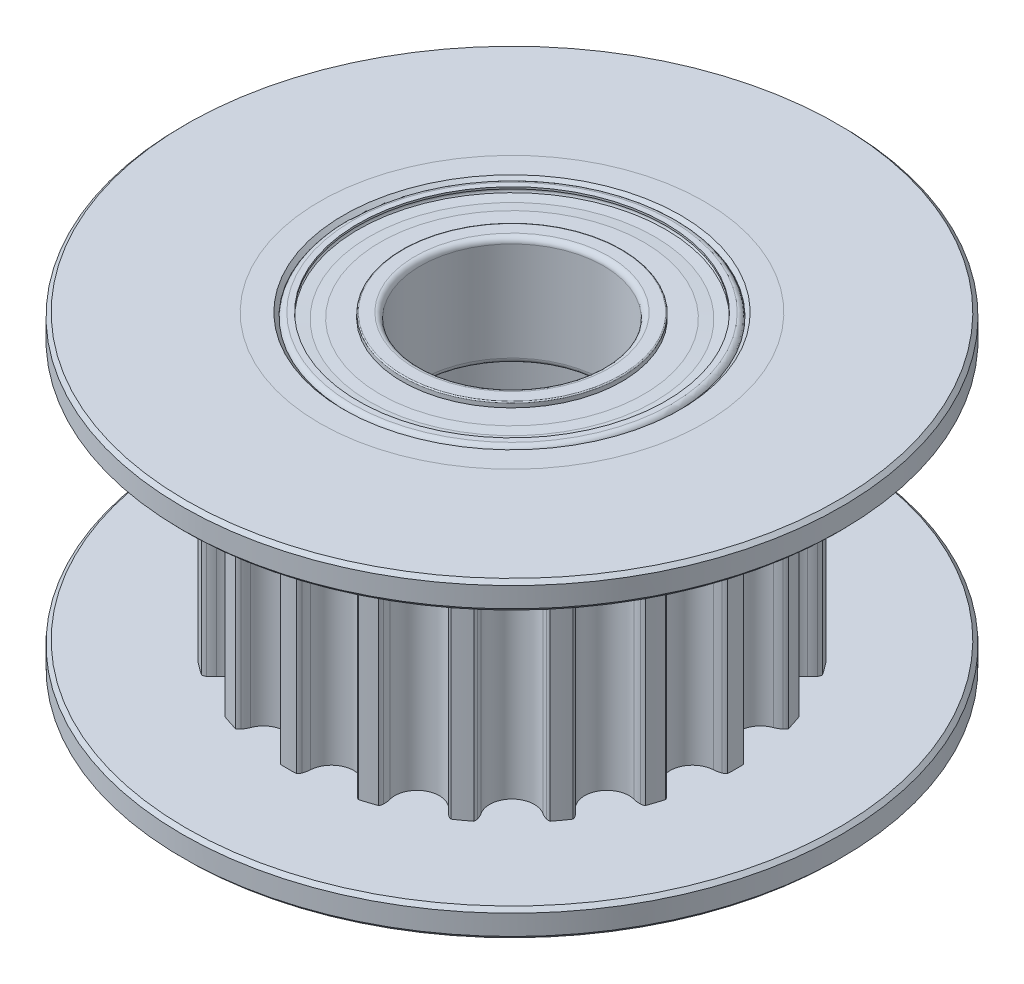
SolidWorks part; units mm, degrees
material "6061-T6 (SS)"
ref_plane "Přední rovina" through (0, 0, 0) normal (0, 0, 1) x (1, 0, 0)
ref_plane "Horní rovina" through (0, 0, 0) normal (0, 1, 0) x (1, 0, 0)
ref_plane "Pravá rovina" through (0, 0, 0) normal (1, 0, 0) x (0, 0, -1)
sketch "Skica1" plane through (0, 0, 0) normal (0, 0, 1) x (1, 0, 0)
  line L0 (4.5, 8.5) -> (5.25, 8.5)
  line L1 (5.25, 8.5) -> (5.25, 7.75)
  line L2 (5.25, 7.75) -> (6.11, 7.75)
  line L3 (6.11, 7.75) -> (6.11, 0.75)
  line L4 (6.11, 0.75) -> (5.25, 0.75)
  line L5 (5.25, 0.75) -> (5.25, 0)
  line L6 (5.25, 0) -> (4.5, 0)
  line L8 (4.5, 8.5) -> (4.5, 5.5)
  line L9 (4.5, 5.5) -> (3.5, 5.5)
  line L10 (3.5, 5.5) -> (3.5, 3)
  line L11 (3.5, 3) -> (4.5, 3)
  line L12 (4.5, 3) -> (4.5, 0)
  line L13 (0, 0) -> (0, -4.1646) construction
  dimension "D1" = 8.5
  dimension "D2" = 7
  dimension "D3" = 4.5
  dimension "D4" = 3.5
  dimension "D5" = 6.11
  dimension "D6" = 3
  dimension "D7" = 5.25
revolve "Rotovat1" add sketch "Skica1" angle 360 about L13
chamfer "Zkosení1" distance 0.1 angle 45 4 edges at (0, 3, 3.5) (0, 0, 4.5) (0, 5.5, 3.5) (0, 8.5, 4.5)
fillet "Zaoblit1" radius 0.1 2 edges at (0, 3, 4.5) (0, 5.5, 4.5)
sketch "Skica11" plane through (0, 7.75, 0) normal (0, 1, 0) x (1, 0, 0)
  line L0 (0, -55) -> (0, 55) construction
  line L1 (-55, 0) -> (55, 0) construction
  point P5 (0, 6.1087)
  arc B0 (-3.6824, -4.5256) -> (-4.5256, -3.6824) centre (-4.1938, -4.1938) ccw
  arc B1 (-3.6824, -4.5256) -> (-3.7624, -4.7003) centre (-3.1284, -4.885) ccw
  arc B2 (-3.7624, -4.7003) -> (-3.7672, -4.8088) centre (-3.5429, -4.7643) ccw
  arc B3 (-3.7672, -4.8088) -> (-3.4093, -5.0688) centre (0, 0) ccw
  arc B4 (-3.4093, -5.0688) -> (-3.3076, -5.0308) centre (-3.4362, -4.8418) ccw
  arc B5 (-3.3076, -5.0308) -> (-3.1662, -4.9006) centre (-3.6792, -4.4848) ccw
  arc B6 (-2.1037, -5.442) -> (-3.1662, -4.9006) centre (-2.6926, -5.2845) ccw
  arc B7 (-2.1037, -5.442) -> (-2.1258, -5.6329) centre (-1.4657, -5.6126) ccw
  arc B8 (-2.1258, -5.6329) -> (-2.0968, -5.7376) centre (-1.8973, -5.6259) ccw
  arc B9 (-2.0968, -5.7376) -> (-1.6761, -5.8742) centre (0, 0) ccw
  arc B10 (-1.6761, -5.8742) -> (-1.5911, -5.8066) centre (-1.7719, -5.6667) ccw
  arc B11 (-1.5911, -5.8066) -> (-1.4968, -5.6392) centre (-2.1132, -5.4022) ccw
  arc B12 (-0.319, -5.8257) -> (-1.4968, -5.6392) centre (-0.9278, -5.8579) ccw
  arc B13 (-0.319, -5.8257) -> (-0.2811, -6.0141) centre (0.3404, -5.7909) ccw
  arc B14 (-0.2811, -6.0141) -> (-0.2211, -6.1047) centre (-0.0659, -5.9369) ccw
  arc B15 (-0.2211, -6.1047) -> (0.2211, -6.1047) centre (0, 0) ccw
  arc B16 (0.2211, -6.1047) -> (0.2811, -6.0141) centre (0.0659, -5.9369) ccw
  arc B17 (0.2811, -6.0141) -> (0.319, -5.8257) centre (-0.3404, -5.7909) ccw
  arc B18 (1.4968, -5.6392) -> (0.319, -5.8257) centre (0.9278, -5.8579) ccw
  arc B19 (1.4968, -5.6392) -> (1.5911, -5.8066) centre (2.1132, -5.4022) ccw
  arc B20 (1.5911, -5.8066) -> (1.6761, -5.8742) centre (1.7719, -5.6667) ccw
  arc B21 (1.6761, -5.8742) -> (2.0968, -5.7376) centre (0, 0) ccw
  arc B22 (2.0968, -5.7376) -> (2.1258, -5.6329) centre (1.8973, -5.6259) ccw
  arc B23 (2.1258, -5.6329) -> (2.1037, -5.442) centre (1.4657, -5.6126) ccw
  arc B24 (3.1662, -4.9006) -> (2.1037, -5.442) centre (2.6926, -5.2845) ccw
  arc B25 (3.1662, -4.9006) -> (3.3076, -5.0308) centre (3.6792, -4.4848) ccw
  arc B26 (3.3076, -5.0308) -> (3.4093, -5.0688) centre (3.4362, -4.8418) ccw
  arc B27 (3.4093, -5.0688) -> (3.7672, -4.8088) centre (0, 0) ccw
  arc B28 (3.7672, -4.8088) -> (3.7624, -4.7003) centre (3.5429, -4.7643) ccw
  arc B29 (3.7624, -4.7003) -> (3.6824, -4.5256) centre (3.1284, -4.885) ccw
  arc B30 (4.5256, -3.6824) -> (3.6824, -4.5256) centre (4.1938, -4.1938) ccw
  arc B31 (4.5256, -3.6824) -> (4.7003, -3.7624) centre (4.885, -3.1284) ccw
  arc B32 (4.7003, -3.7624) -> (4.8088, -3.7672) centre (4.7643, -3.5429) ccw
  arc B33 (4.8088, -3.7672) -> (5.0688, -3.4093) centre (0, 0) ccw
  arc B34 (5.0688, -3.4093) -> (5.0308, -3.3076) centre (4.8418, -3.4362) ccw
  arc B35 (5.0308, -3.3076) -> (4.9006, -3.1662) centre (4.4848, -3.6792) ccw
  arc B36 (5.442, -2.1037) -> (4.9006, -3.1662) centre (5.2845, -2.6926) ccw
  arc B37 (5.442, -2.1037) -> (5.6329, -2.1258) centre (5.6126, -1.4657) ccw
  arc B38 (5.6329, -2.1258) -> (5.7376, -2.0968) centre (5.6259, -1.8973) ccw
  arc B39 (5.7376, -2.0968) -> (5.8742, -1.6761) centre (0, 0) ccw
  arc B40 (5.8742, -1.6761) -> (5.8066, -1.5911) centre (5.6667, -1.7719) ccw
  arc B41 (5.8066, -1.5911) -> (5.6392, -1.4968) centre (5.4022, -2.1132) ccw
  arc B42 (5.8257, -0.319) -> (5.6392, -1.4968) centre (5.8579, -0.9278) ccw
  arc B43 (5.8257, -0.319) -> (6.0141, -0.2811) centre (5.7909, 0.3404) ccw
  arc B44 (6.0141, -0.2811) -> (6.1047, -0.2211) centre (5.9369, -0.0659) ccw
  arc B45 (6.1047, -0.2211) -> (6.1047, 0.2211) centre (0, 0) ccw
  arc B46 (6.1047, 0.2211) -> (6.0141, 0.2811) centre (5.9369, 0.0659) ccw
  arc B47 (6.0141, 0.2811) -> (5.8257, 0.319) centre (5.7909, -0.3404) ccw
  arc B48 (5.6392, 1.4968) -> (5.8257, 0.319) centre (5.8579, 0.9278) ccw
  arc B49 (5.6392, 1.4968) -> (5.8066, 1.5911) centre (5.4022, 2.1132) ccw
  arc B50 (5.8066, 1.5911) -> (5.8742, 1.6761) centre (5.6667, 1.7719) ccw
  arc B51 (5.8742, 1.6761) -> (5.7376, 2.0968) centre (0, 0) ccw
  arc B52 (5.7376, 2.0968) -> (5.6329, 2.1258) centre (5.6259, 1.8973) ccw
  arc B53 (5.6329, 2.1258) -> (5.442, 2.1037) centre (5.6126, 1.4657) ccw
  arc B54 (4.9006, 3.1662) -> (5.442, 2.1037) centre (5.2845, 2.6926) ccw
  arc B55 (4.9006, 3.1662) -> (5.0308, 3.3076) centre (4.4848, 3.6792) ccw
  arc B56 (5.0308, 3.3076) -> (5.0688, 3.4093) centre (4.8418, 3.4362) ccw
  arc B57 (5.0688, 3.4093) -> (4.8088, 3.7672) centre (0, 0) ccw
  arc B58 (4.8088, 3.7672) -> (4.7003, 3.7624) centre (4.7643, 3.5429) ccw
  arc B59 (4.7003, 3.7624) -> (4.5256, 3.6824) centre (4.885, 3.1284) ccw
  arc B60 (3.6824, 4.5256) -> (4.5256, 3.6824) centre (4.1938, 4.1938) ccw
  arc B61 (3.6824, 4.5256) -> (3.7624, 4.7003) centre (3.1284, 4.885) ccw
  arc B62 (3.7624, 4.7003) -> (3.7672, 4.8088) centre (3.5429, 4.7643) ccw
  arc B63 (3.7672, 4.8088) -> (3.4093, 5.0688) centre (0, 0) ccw
  arc B64 (3.4093, 5.0688) -> (3.3076, 5.0308) centre (3.4362, 4.8418) ccw
  arc B65 (3.3076, 5.0308) -> (3.1662, 4.9006) centre (3.6792, 4.4848) ccw
  arc B66 (2.1037, 5.442) -> (3.1662, 4.9006) centre (2.6926, 5.2845) ccw
  arc B67 (2.1037, 5.442) -> (2.1258, 5.6329) centre (1.4657, 5.6126) ccw
  arc B68 (2.1258, 5.6329) -> (2.0968, 5.7376) centre (1.8973, 5.6259) ccw
  arc B69 (2.0968, 5.7376) -> (1.6761, 5.8742) centre (0, 0) ccw
  arc B70 (1.6761, 5.8742) -> (1.5911, 5.8066) centre (1.7719, 5.6667) ccw
  arc B71 (1.5911, 5.8066) -> (1.4968, 5.6392) centre (2.1132, 5.4022) ccw
  arc B72 (0.319, 5.8257) -> (1.4968, 5.6392) centre (0.9278, 5.8579) ccw
  arc B73 (0.319, 5.8257) -> (0.2811, 6.0141) centre (-0.3404, 5.7909) ccw
  arc B74 (0.2811, 6.0141) -> (0.2211, 6.1047) centre (0.0659, 5.9369) ccw
  arc B75 (0.2211, 6.1047) -> (-0.2211, 6.1047) centre (0, 0) ccw
  arc B76 (-0.2211, 6.1047) -> (-0.2811, 6.0141) centre (-0.0659, 5.9369) ccw
  arc B77 (-0.2811, 6.0141) -> (-0.319, 5.8257) centre (0.3404, 5.7909) ccw
  arc B78 (-1.4968, 5.6392) -> (-0.319, 5.8257) centre (-0.9278, 5.8579) ccw
  arc B79 (-1.4968, 5.6392) -> (-1.5911, 5.8066) centre (-2.1132, 5.4022) ccw
  arc B80 (-1.5911, 5.8066) -> (-1.6761, 5.8742) centre (-1.7719, 5.6667) ccw
  arc B81 (-1.6761, 5.8742) -> (-2.0968, 5.7376) centre (0, 0) ccw
  arc B82 (-2.0968, 5.7376) -> (-2.1258, 5.6329) centre (-1.8973, 5.6259) ccw
  arc B83 (-2.1258, 5.6329) -> (-2.1037, 5.442) centre (-1.4657, 5.6126) ccw
  arc B84 (-3.1662, 4.9006) -> (-2.1037, 5.442) centre (-2.6926, 5.2845) ccw
  arc B85 (-3.1662, 4.9006) -> (-3.3076, 5.0308) centre (-3.6792, 4.4848) ccw
  arc B86 (-3.3076, 5.0308) -> (-3.4093, 5.0688) centre (-3.4362, 4.8418) ccw
  arc B87 (-3.4093, 5.0688) -> (-3.7672, 4.8088) centre (0, 0) ccw
  arc B88 (-3.7672, 4.8088) -> (-3.7624, 4.7003) centre (-3.5429, 4.7643) ccw
  arc B89 (-3.7624, 4.7003) -> (-3.6824, 4.5256) centre (-3.1284, 4.885) ccw
  arc B90 (-4.5256, 3.6824) -> (-3.6824, 4.5256) centre (-4.1938, 4.1938) ccw
  arc B91 (-4.5256, 3.6824) -> (-4.7003, 3.7624) centre (-4.885, 3.1284) ccw
  arc B92 (-4.7003, 3.7624) -> (-4.8088, 3.7672) centre (-4.7643, 3.5429) ccw
  arc B93 (-4.8088, 3.7672) -> (-5.0688, 3.4093) centre (0, 0) ccw
  arc B94 (-5.0688, 3.4093) -> (-5.0308, 3.3076) centre (-4.8418, 3.4362) ccw
  arc B95 (-5.0308, 3.3076) -> (-4.9006, 3.1662) centre (-4.4848, 3.6792) ccw
  arc B96 (-5.442, 2.1037) -> (-4.9006, 3.1662) centre (-5.2845, 2.6926) ccw
  arc B97 (-5.442, 2.1037) -> (-5.6329, 2.1258) centre (-5.6126, 1.4657) ccw
  arc B98 (-5.6329, 2.1258) -> (-5.7376, 2.0968) centre (-5.6259, 1.8973) ccw
  arc B99 (-5.7376, 2.0968) -> (-5.8742, 1.6761) centre (0, 0) ccw
  arc B100 (-5.8742, 1.6761) -> (-5.8066, 1.5911) centre (-5.6667, 1.7719) ccw
  arc B101 (-5.8066, 1.5911) -> (-5.6392, 1.4968) centre (-5.4022, 2.1132) ccw
  arc B102 (-5.8257, 0.319) -> (-5.6392, 1.4968) centre (-5.8579, 0.9278) ccw
  arc B103 (-5.8257, 0.319) -> (-6.0141, 0.2811) centre (-5.7909, -0.3404) ccw
  arc B104 (-6.0141, 0.2811) -> (-6.1047, 0.2211) centre (-5.9369, 0.0659) ccw
  arc B105 (-6.1047, 0.2211) -> (-6.1047, -0.2211) centre (0, 0) ccw
  arc B106 (-6.1047, -0.2211) -> (-6.0141, -0.2811) centre (-5.9369, -0.0659) ccw
  arc B107 (-6.0141, -0.2811) -> (-5.8257, -0.319) centre (-5.7909, 0.3404) ccw
  arc B108 (-5.6392, -1.4968) -> (-5.8257, -0.319) centre (-5.8579, -0.9278) ccw
  arc B109 (-5.6392, -1.4968) -> (-5.8066, -1.5911) centre (-5.4022, -2.1132) ccw
  arc B110 (-5.8066, -1.5911) -> (-5.8742, -1.6761) centre (-5.6667, -1.7719) ccw
  arc B111 (-5.8742, -1.6761) -> (-5.7376, -2.0968) centre (0, 0) ccw
  arc B112 (-5.7376, -2.0968) -> (-5.6329, -2.1258) centre (-5.6259, -1.8973) ccw
  arc B113 (-5.6329, -2.1258) -> (-5.442, -2.1037) centre (-5.6126, -1.4657) ccw
  arc B114 (-4.9006, -3.1662) -> (-5.442, -2.1037) centre (-5.2845, -2.6926) ccw
  arc B115 (-4.9006, -3.1662) -> (-5.0308, -3.3076) centre (-4.4848, -3.6792) ccw
  arc B116 (-5.0308, -3.3076) -> (-5.0688, -3.4093) centre (-4.8418, -3.4362) ccw
  arc B117 (-5.0688, -3.4093) -> (-4.8088, -3.7672) centre (0, 0) ccw
  arc B118 (-4.8088, -3.7672) -> (-4.7003, -3.7624) centre (-4.7643, -3.5429) ccw
  arc B119 (-4.7003, -3.7624) -> (-4.5256, -3.6824) centre (-4.885, -3.1284) ccw
sketch_block_instance "Blok1-1"
sketch_block "Blok1"
extrude "Odebrat vysunutím1" cut sketch "Skica11" against normal through all flip side to cut
sketch "Skica10" plane through (0, 8.5, 0) normal (0, 1, 0) x (1, 0, 0)
  circle A0 centre (0, 0) radius 9
  circle A1 centre (0, 0) radius 5.25 construction
  circle A2 centre (0, 0) radius 5.25
  dimension "D1" = 18
extrude "Přidat vysunutím1" add sketch "Skica10" against normal up to surface (0.75 mm away) separate body up to face at (0, 7.75, 5.25)
sketch "Skica12" plane through (0, 0, 0) normal (0, -1, 0) x (1, 0, 0)
  circle A0 centre (0, 0) radius 9
  circle A1 centre (0, 0) radius 5.25 construction
  circle A2 centre (0, 0) radius 5.25
  circle A3 centre (0, 0) radius 9 construction
extrude "Přidat vysunutím2" add sketch "Skica12" against normal up to surface (0.75 mm away) separate body up to face at (0, 0.75, 5.25)
chamfer "Zkosení2" distance 0.1 angle 45 2 edges at (0, 7.75, -9) (0, 8.5, 9)
chamfer "Zkosení3" distance 0.1 angle 45 2 edges at (0, 0, -9) (0, 0.75, 9)
sketch "Skica4" plane through (0, 0, 0) normal (0, 0, 1) x (1, 0, 0)
  line L0 (4.5, 8.35) -> (4.5, 5.65)
  line L1 (4.35, 5.5) -> (4.2, 5.5)
  line L2 (4.2, 5.5) -> (4.2, 5.55)
  line L3 (3.85, 5.7828) -> (4.2132, 5.729)
  line L4 (3.85, 5.7828) -> (3.85, 6.5528)
  line L5 (3.85, 7.4472) -> (3.85, 8.2172)
  line L6 (3.85, 8.2172) -> (4.2132, 8.271)
  line L7 (4.35, 8.5) -> (4.2, 8.5)
  line L8 (4.2, 8.5) -> (4.2, 8.45)
  line L9 (0, 0) -> (0, 18.4294) construction
  line L10 (4.4, 5.5) -> (-4.4, 5.5) construction
  arc A0 (4.35, 8.5) -> (4.5, 8.35) centre (4.35, 8.35) cw
  arc A1 (4.35, 5.5) -> (4.5, 5.65) centre (4.35, 5.65) ccw
  arc A2 (4.2, 8.45) -> (4.2132, 8.271) centre (4.2, 8.36) cw
  arc A3 (3.85, 7.4472) -> (3.85, 6.5528) centre (3.45, 7) cw
  arc A4 (4.2, 5.55) -> (4.2132, 5.729) centre (4.2, 5.64) ccw
  point P26 (4.5, 7)
  point P29 (4.275, 5.5)
  dimension "D3" = 0.09
  dimension "D6" = 0.15
  dimension "D7" = 0.6
  dimension "D1" = 4.5
  dimension "D2" = 3.85
  dimension "D4" = 0.05
  dimension "D5" = 0.15
  dimension "D8" = 0.77
  dimension "D9" = 3
  dimension "D10" = 1.05
revolve "Rotovat2" add sketch "Skica4" angle 360 about L9
sketch "Skica5" plane through (0, 0, 0) normal (0, 0, 1) x (1, 0, 0)
  line L0 (2.5, 8.35) -> (2.5, 5.65)
  line L1 (2.65, 8.5) -> (2.97, 8.5)
  line L2 (3, 8.47) -> (3, 8.36)
  line L3 (3, 8.36) -> (3.6, 8.36)
  line L4 (3.6, 8.36) -> (3.9, 8.34)
  line L5 (3.9, 8.34) -> (4.2, 8.36)
  line L6 (4.2, 8.36) -> (4.2, 8.31)
  line L7 (4.2, 8.31) -> (3.9, 8.27)
  line L8 (3.9, 8.27) -> (3.6, 8.27)
  line L9 (3.6, 8.27) -> (3, 8.31)
  line L10 (3, 8.31) -> (3, 7.3969)
  line L11 (2.65, 5.5) -> (2.97, 5.5)
  line L12 (0, 0) -> (0, 20.363) construction
  line L13 (3, 5.53) -> (3, 5.64)
  line L21 (3, 5.69) -> (3, 6.6031)
  line L22 (3, 5.64) -> (3.6, 5.64)
  line L23 (3.6, 5.64) -> (3.8962, 5.6917)
  line L24 (3.8962, 5.6917) -> (4.1924, 5.64)
  line L25 (4.1924, 5.64) -> (4.1924, 5.69)
  line L26 (4.1924, 5.69) -> (3.8975, 5.7581)
  line L27 (3.8975, 5.7581) -> (3.5975, 5.7581)
  line L28 (3.5975, 5.7581) -> (3, 5.69)
  line L29 (-4.2, 5.5) -> (4.2, 5.5) construction
  arc A0 (2.65, 5.5) -> (2.5, 5.65) centre (2.65, 5.65) cw
  arc A1 (2.65, 8.5) -> (2.5, 8.35) centre (2.65, 8.35) ccw
  arc A2 (3, 8.47) -> (2.97, 8.5) centre (2.97, 8.47) ccw
  arc A3 (3, 5.53) -> (2.97, 5.5) centre (2.97, 5.53) cw
  arc A4 (3, 7.3969) -> (3, 6.6031) centre (3.45, 7) ccw
  dimension "D3" = 0.15
  dimension "D4" = 0.11
  dimension "D5" = 0.03
  dimension "D7" = 0.6
  dimension "D1" = 2.5
  dimension "D2" = 3
  dimension "D6" = 0.6
  dimension "D8" = 0.95
  dimension "D9" = 3
  dimension "D10" = 1.2
  dimension "D11" = 0.3
  dimension "D12" = 0.05
  dimension "D13" = 0.9
  dimension "D14" = 0.6
  dimension "D15" = 0.09
  dimension "D16" = 0.05
  dimension "D17" = 0.05
revolve "Rotovat3" add sketch "Skica5" angle 360 about L12
sketch "Skica6" plane through (0, 0, 0) normal (0, 0, 1) x (1, 0, 0)
  line L0 (3.45, 7.6) -> (3.45, 6.4)
  line L4 (-4.2, 5.5) -> (4.2, 5.5) construction
  arc A0 (3.45, 7.6) -> (3.45, 6.4) centre (3.45, 7) cw
  dimension "D1" = 0.6
  dimension "D2" = 1.5
  dimension "D3" = 3.45
revolve "Rotovat4" add sketch "Skica6" angle 360 about L0
pattern_circular "Kruhové pole1" count 8 over 360 about axis through (0, 0, 0) along (0, 1, 0) of bodies 105
sketch "Skica7" plane through (0, 0, 0) normal (0, 0, 1) x (1, 0, 0)
  line L0 (4.5, 2.85) -> (4.5, 0.15)
  line L1 (4.35, 0) -> (4.2, 0)
  line L2 (4.2, 0) -> (4.2, 0.05)
  line L3 (3.85, 0.2828) -> (4.2132, 0.229)
  line L4 (3.85, 0.2828) -> (3.85, 1.0528)
  line L5 (3.85, 1.9472) -> (3.85, 2.7172)
  line L6 (3.85, 2.7172) -> (4.2132, 2.771)
  line L7 (4.35, 3) -> (4.2, 3)
  line L8 (4.2, 3) -> (4.2, 2.95)
  line L9 (0, 0) -> (0, 11.2374) construction
  arc A0 (4.35, 3) -> (4.5, 2.85) centre (4.35, 2.85) cw
  arc A1 (4.35, 0) -> (4.5, 0.15) centre (4.35, 0.15) ccw
  arc A2 (4.2, 2.95) -> (4.2132, 2.771) centre (4.2, 2.86) cw
  arc A3 (3.85, 1.9472) -> (3.85, 1.0528) centre (3.45, 1.5) cw
  arc A4 (4.2, 0.05) -> (4.2132, 0.229) centre (4.2, 0.14) ccw
  point P19 (4.5, 1.5)
  point P20 (4.275, 0)
  dimension "D1" = 0.09
  dimension "D4" = 0.15
  dimension "D5" = 0.6
  dimension "D2" = 0.05
  dimension "D3" = 0.15
  dimension "D6" = 0.77
  dimension "D7" = 3
  dimension "D8" = 1.05
  dimension "D9" = 4.5
  dimension "D10" = 3.85
revolve "Rotovat5" add sketch "Skica7" angle 360 about L9
sketch "Skica8" plane through (0, 0, 0) normal (0, 0, 1) x (1, 0, 0)
  line L0 (2.5, 2.85) -> (2.5, 0.15)
  line L1 (2.65, 3) -> (2.97, 3)
  line L2 (3, 2.97) -> (3, 2.86)
  line L3 (3, 2.86) -> (3.6, 2.86)
  line L4 (3.6, 2.86) -> (3.9, 2.84)
  line L5 (3.9, 2.84) -> (4.2, 2.86)
  line L6 (4.2, 2.86) -> (4.2, 2.81)
  line L7 (4.2, 2.81) -> (3.9, 2.77)
  line L8 (3.9, 2.77) -> (3.6, 2.77)
  line L9 (3.6, 2.77) -> (3, 2.81)
  line L10 (3, 2.81) -> (3, 1.8969)
  line L11 (2.65, 0) -> (2.97, 0)
  line L12 (3, 0.03) -> (3, 0.14)
  line L13 (3, 0.19) -> (3, 1.1031)
  line L14 (3, 0.14) -> (3.6, 0.14)
  line L15 (3.6, 0.14) -> (3.8962, 0.1917)
  line L16 (3.8962, 0.1917) -> (4.1924, 0.14)
  line L17 (4.1924, 0.14) -> (4.1924, 0.19)
  line L18 (4.1924, 0.19) -> (3.8975, 0.2581)
  line L19 (3.8975, 0.2581) -> (3.5975, 0.2581)
  line L20 (3.5975, 0.2581) -> (3, 0.19)
  line L21 (0, 0) -> (0, -2.9362) construction
  arc A0 (2.65, 0) -> (2.5, 0.15) centre (2.65, 0.15) cw
  arc A1 (2.65, 3) -> (2.5, 2.85) centre (2.65, 2.85) ccw
  arc A2 (3, 2.97) -> (2.97, 3) centre (2.97, 2.97) ccw
  arc A3 (3, 0.03) -> (2.97, 0) centre (2.97, 0.03) cw
  arc A4 (3, 1.8969) -> (3, 1.1031) centre (3.45, 1.5) ccw
  dimension "D1" = 0.15
  dimension "D2" = 0.03
  dimension "D5" = 0.6
  dimension "D3" = 0.11
  dimension "D4" = 0.6
  dimension "D6" = 0.95
  dimension "D7" = 3
  dimension "D8" = 1.2
  dimension "D9" = 0.3
  dimension "D10" = 0.05
  dimension "D11" = 0.9
  dimension "D12" = 0.6
  dimension "D13" = 0.09
  dimension "D14" = 0.05
  dimension "D15" = 0.05
  dimension "D16" = 2.5
  dimension "D17" = 3
revolve "Rotovat6" add sketch "Skica8" angle 360 about L21
sketch "Skica9" plane through (0, 0, 0) normal (0, 0, 1) x (1, 0, 0)
  line L0 (3.45, 2.1) -> (3.45, 0.9)
  line L1 (0, -2.351) -> (0, 5.6956) construction
  arc A0 (3.45, 2.1) -> (3.45, 0.9) centre (3.45, 1.5) cw
  dimension "D1" = 0.6
  dimension "D2" = 3.45
  dimension "D3" = 1.5
revolve "Rotovat7" add sketch "Skica9" angle 360 about L0
pattern_circular "Kruhové pole3" count 8 over 360 about axis through (0, 0, 0) along (0, 1, 0) reverse direction yes of bodies 123
